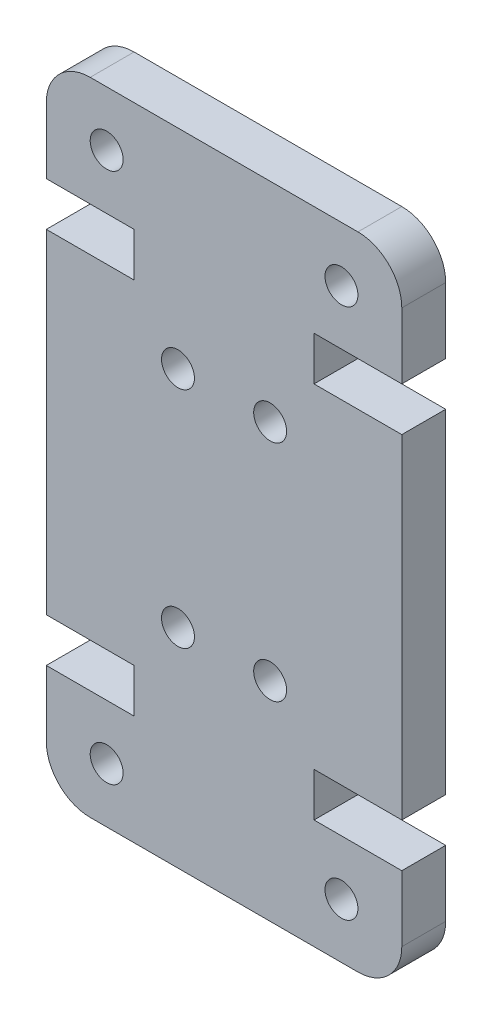
SolidWorks part; units mm, degrees
ref_plane "Front Plane" through (0, 0, 0) normal (0, 0, 1) x (1, 0, 0)
ref_plane "Top Plane" through (0, 0, 0) normal (0, 1, 0) x (1, 0, 0)
ref_plane "Right Plane" through (0, 0, 0) normal (1, 0, 0) x (0, 0, -1)
sketch "Sketch1" plane through (0, 0, 0) normal (0, 0, 1) x (1, 0, 0)
  line L0 (0, 22.21) -> (0, 7)
  line L1 (16.2, 22.21) -> (16.2, 7)
  line L2 (2, 29.21) -> (14.2, 29.21)
  line L3 (2, 0) -> (14.2, 0)
  line L4 (4, 24.21) -> (4, 22.21)
  line L5 (0, 24.21) -> (4, 24.21)
  line L6 (4, 22.21) -> (0, 22.21)
  line L7 (4, 7) -> (4, 5)
  line L8 (0, 27.21) -> (0, 24.21)
  line L9 (16.2, 24.21) -> (16.2, 27.21)
  line L10 (0, 7) -> (4, 7)
  line L11 (12.2, 24.21) -> (12.2, 22.21)
  line L12 (4, 5) -> (0, 5)
  line L13 (12.2, 22.21) -> (16.2, 22.21)
  line L14 (16.2, 24.21) -> (12.2, 24.21)
  line L15 (12.2, 7) -> (12.2, 5)
  line L16 (0, 2) -> (0, 5)
  line L17 (16.2, 5) -> (16.2, 2)
  line L18 (12.2, 5) -> (16.2, 5)
  line L19 (16.2, 7) -> (12.2, 7)
  arc A0 (16.2, 27.21) -> (14.2, 29.21) centre (14.2, 27.21) ccw
  arc A1 (2, 29.21) -> (0, 27.21) centre (2, 27.21) ccw
  circle A2 centre (10.2, 19.71) radius 0.75
  circle A3 centre (6, 19.71) radius 0.75
  arc A4 (14.2, 0) -> (16.2, 2) centre (14.2, 2) ccw
  arc A5 (0, 2) -> (2, 0) centre (2, 2) ccw
  circle A6 centre (10.2, 9.5) radius 0.75
  circle A7 centre (6, 9.5) radius 0.75
  circle A8 centre (13.45, 2.5) radius 0.75
  circle A9 centre (2.75, 2.5) radius 0.75
  circle A10 centre (13.45, 26.71) radius 0.75
  circle A11 centre (2.75, 26.71) radius 0.75
extrude "Boss-Extrude1" add sketch "Sketch1" along normal blind 2
